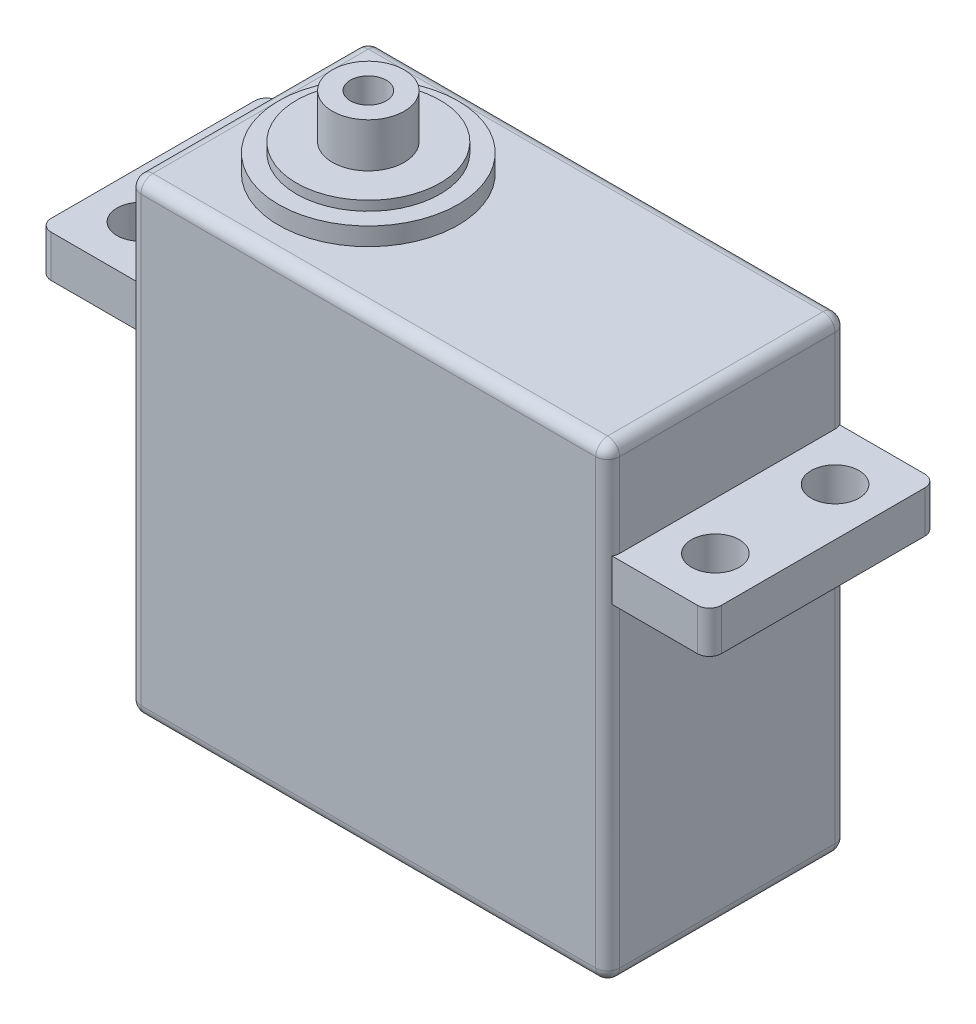
SolidWorks part; units mm, degrees
ref_plane "前视基准面" through (0, 0, 0) normal (0, 0, 1) x (1, 0, 0)
ref_plane "上视基准面" through (0, 0, 0) normal (0, 1, 0) x (1, 0, 0)
ref_plane "右视基准面" through (0, 0, 0) normal (1, 0, 0) x (0, 0, -1)
other "Configuration Table"
sketch "草图1" plane through (0, 0, 0) normal (0, 0, 1) x (1, 0, 0)
  line L1 (-20, -19.5) -> (20, -19.5)
  line L2 (-20, -19.5) -> (-20, 19.5)
  line L3 (-20, 19.5) -> (20, 19.5)
  line L4 (20, -19.5) -> (20, 19.5)
  line L5 (-20, -19.5) -> (20, 19.5) construction
  line L6 (-20, 19.5) -> (20, -19.5) construction
  point P0 (0, 0)
  dimension "D1" = 40
  dimension "D2" = 39
extrude "凸台-拉伸1" add sketch "草图1" along normal blind 20
ref_plane "基准面1" through (0, 0, 10) normal (0, 0, -1) x (-1, 0, 0)
sketch "草图3" plane through (0, 0, 10) normal (0, 0, -1) x (-1, 0, 0)
sketch "草图4" plane through (0, 0, 10) normal (0, 0, -1) x (-1, 0, 0)
  line L0 (20, -19.5) -> (20, 19.5) construction
  line L1 (20, 11.5) -> (28, 11.5)
  line L2 (20, 11.5) -> (20, 8)
  line L3 (20, 8) -> (28, 8)
  line L4 (28, 11.5) -> (28, 8)
  line L5 (20, -19.5) -> (-20, -19.5) construction
  line L6 (0, 0) -> (0, 19.5) construction
  line L7 (20, -19.5) -> (-20, 19.5) construction
  line L8 (20, 19.5) -> (-20, 19.5) construction
  line L9 (-28, 11.5) -> (-28, 8)
  line L10 (-20, 8) -> (-28, 8)
  line L11 (-20, 11.5) -> (-20, 8)
  line L12 (-20, 11.5) -> (-28, 11.5)
  dimension "D1" = 3.5
  dimension "D2" = 8
  dimension "D3" = 31
extrude "凸台-拉伸2" add sketch "草图4" along normal mid plane 19
sketch "草图6" plane through (0, 11.5, 0) normal (0, 1, 0) x (1, 0, 0)
  line L0 (0, 0) -> (0, -20) construction
  line L1 (20, -20) -> (-20, -20) construction
  line L2 (0, -10) -> (-28, -10) construction
  line L3 (-28, -0.5) -> (-28, -19.5) construction
  circle A0 centre (-24, -5) radius 2
  circle A1 centre (-24, -15) radius 2
  circle A2 centre (24, -15) radius 2
  circle A3 centre (24, -5) radius 2
  dimension "D1" = 4
  dimension "D2" = 10
  dimension "D3" = 48
extrude "切除-拉伸1" cut sketch "草图6" against normal blind 19
sketch "草图7" plane through (0, 19.5, 0) normal (0, 1, 0) x (1, 0, 0)
  line L0 (-20, -10) -> (20, -10) construction
  line L1 (-20, -20) -> (-20, 0) construction
  line L2 (20, -20) -> (20, 0) construction
  circle A0 centre (-10, -10) radius 7.5
  dimension "D1" = 15
  dimension "D2" = 14
extrude "凸台-拉伸3" add sketch "草图7" along normal blind 1.5
ref_plane "基准面2" through (0, 25.5, 0) normal (0, -1, 0) x (-1, 0, 0)
sketch "草图8" plane through (0, 21, 0) normal (0, 1, 0) x (1, 0, 0)
  circle A0 centre (-10, -10) radius 6
  dimension "D1" = 12
extrude "凸台-拉伸4" add sketch "草图8" along normal blind 0.8
sketch "草图9" plane through (0, 21.8, 0) normal (0, 1, 0) x (1, 0, 0)
  circle A0 centre (-10, -10) radius 3
  dimension "D1" = 6
extrude "凸台-拉伸5" add sketch "草图9" along normal up to surface (3.7 mm away) up to plane "基准面2"
sketch "草图10" plane through (0, 25.5, 0) normal (0, 1, 0) x (1, 0, 0)
  circle A0 centre (-10, -10) radius 1.5 construction
  dimension "D1" = 3
sketch "草图11" plane through (0, 25.5, 0) normal (0, 1, 0) x (1, 0, 0)
  point P0 (-10, -10)
  point P3 (-10, -10)
hole_wizard "Ø3.0mm 暗销孔1" positions "草图11" profile "草图12" hole size "Ø3.0" standard "GB"
sketch "草图12" plane through (-10, 25.5, 10) normal (1, 0, 0) x (0, 0, 1)
  line L0 (0, 0) -> (0, 8.9013)
  line L1 (0, 8.9013) -> (1.5, 8)
  line L2 (1.5, 8) -> (1.5, 0)
  line L5 (1.5, 0) -> (0, 0)
  line L10 (0, 8.9013) -> (-1.5, 8) construction
  line L11 (0, -6.35) -> (0, 107.95) construction
  dimension "孔直径" = 3
  dimension "孔深度" = 8
  dimension "导头角度" = 118
cosmetic thread "装饰螺纹线1" parameters "D2"=4.5
fillet "圆角1" radius 1 16 edges at (-20, -19.5, 10) (0, -19.5, 20) (20, -19.5, 10) (0, -19.5, 0) (-20, 19.5, 10) (0, 19.5, 20) (20, 19.5, 10) (0, 19.5, 0) (-20, 0, 0) (-20, 0, 20) (20, 0, 20) (20, 0, 0) (28, 9.75, 0.5) (28, 9.75, 19.5) (-28, 9.75, 0.5) (-28, 9.75, 19.5)
